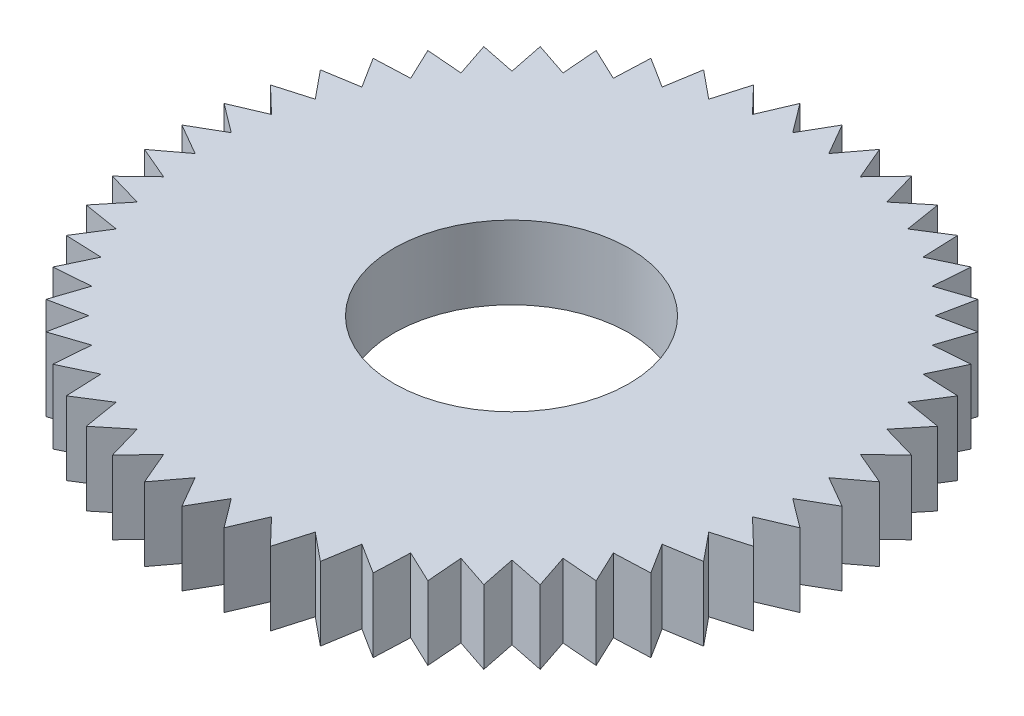
SolidWorks part; units mm, degrees
ref_plane "Front Plane" through (0, 0, 0) normal (0, 0, 1) x (1, 0, 0)
ref_plane "Top Plane" through (0, 0, 0) normal (0, 1, 0) x (1, 0, 0)
ref_plane "Right Plane" through (0, 0, 0) normal (1, 0, 0) x (0, 0, -1)
sketch "Sketch1" plane through (0, 0, 0) normal (0, 1, 0) x (1, 0, 0)
  line L0 (0, 0) -> (0, 11.2593) construction
  line L1 (0, 11.2593) -> (-0.6156, 10.1931)
  line L122 (0, 11.2593) -> (0.6156, 10.1931)
  line L123 (1.3552, 11.1774) -> (0.6156, 10.1931)
  line L124 (1.3552, 11.1774) -> (1.8377, 10.0447)
  line L125 (2.6906, 10.9326) -> (1.8377, 10.0447)
  line L126 (2.6906, 10.9326) -> (3.0331, 9.7501)
  line L127 (3.9867, 10.5287) -> (3.0331, 9.7501)
  line L128 (3.9867, 10.5287) -> (4.1842, 9.3135)
  line L129 (5.2248, 9.9715) -> (4.1842, 9.3135)
  line L130 (5.2248, 9.9715) -> (5.2744, 8.7414)
  line L131 (6.3866, 9.2692) -> (5.2744, 8.7414)
  line L132 (6.3866, 9.2692) -> (6.2876, 8.042)
  line L133 (7.4553, 8.4319) -> (6.2876, 8.042)
  line L134 (7.4553, 8.4319) -> (7.2091, 7.2256)
  line L135 (8.4153, 7.4719) -> (7.2091, 7.2256)
  line L136 (8.4153, 7.4719) -> (8.0255, 6.3041)
  line L137 (9.2526, 6.4032) -> (8.0255, 6.3041)
  line L138 (9.2526, 6.4032) -> (8.7248, 5.2909)
  line L139 (9.955, 5.2413) -> (8.7248, 5.2909)
  line L140 (9.955, 5.2413) -> (9.297, 4.2008)
  line L141 (10.5122, 4.0033) -> (9.297, 4.2008)
  line L142 (10.5122, 4.0033) -> (9.7335, 3.0497)
  line L143 (10.9161, 2.7071) -> (9.7335, 3.0497)
  line L144 (10.9161, 2.7071) -> (10.0282, 1.8543)
  line L145 (11.1608, 1.3717) -> (10.0282, 1.8543)
  line L146 (11.1608, 1.3717) -> (10.1766, 0.6321)
  line L147 (11.2428, 0.0166) -> (10.1766, 0.6321)
  line L148 (11.2428, 0.0166) -> (10.1766, -0.599)
  line L149 (11.1608, -1.3386) -> (10.1766, -0.599)
  line L150 (11.1608, -1.3386) -> (10.0282, -1.8212)
  line L151 (10.9161, -2.674) -> (10.0282, -1.8212)
  line L152 (10.9161, -2.674) -> (9.7335, -3.0165)
  line L153 (10.5122, -3.9702) -> (9.7335, -3.0165)
  line L154 (10.5122, -3.9702) -> (9.297, -4.1677)
  line L155 (9.955, -5.2082) -> (9.297, -4.1677)
  line L156 (9.955, -5.2082) -> (8.7248, -5.2578)
  line L157 (9.2526, -6.3701) -> (8.7248, -5.2578)
  line L158 (9.2526, -6.3701) -> (8.0255, -6.271)
  line L159 (8.4153, -7.4388) -> (8.0255, -6.271)
  line L160 (8.4153, -7.4388) -> (7.2091, -7.1925)
  line L161 (7.4553, -8.3988) -> (7.2091, -7.1925)
  line L162 (7.4553, -8.3988) -> (6.2876, -8.0089)
  line L163 (6.3866, -9.2361) -> (6.2876, -8.0089)
  line L164 (6.3866, -9.2361) -> (5.2744, -8.7083)
  line L165 (5.2248, -9.9384) -> (5.2744, -8.7083)
  line L166 (5.2248, -9.9384) -> (4.1842, -9.2804)
  line L167 (3.9867, -10.4956) -> (4.1842, -9.2804)
  line L168 (3.9867, -10.4956) -> (3.0331, -9.717)
  line L169 (2.6906, -10.8995) -> (3.0331, -9.717)
  line L170 (2.6906, -10.8995) -> (1.8377, -10.0116)
  line L171 (1.3552, -11.1442) -> (1.8377, -10.0116)
  line L172 (1.3552, -11.1442) -> (0.6156, -10.16)
  line L173 (0, -11.2262) -> (0.6156, -10.16)
  line L174 (0, -11.2262) -> (-0.6156, -10.16)
  line L175 (-1.3552, -11.1442) -> (-0.6156, -10.16)
  line L176 (-1.3552, -11.1442) -> (-1.8377, -10.0116)
  line L177 (-2.6906, -10.8995) -> (-1.8377, -10.0116)
  line L178 (-2.6906, -10.8995) -> (-3.0331, -9.717)
  line L179 (-3.9867, -10.4956) -> (-3.0331, -9.717)
  line L180 (-3.9867, -10.4956) -> (-4.1842, -9.2804)
  line L181 (-5.2248, -9.9384) -> (-4.1842, -9.2804)
  line L182 (-5.2248, -9.9384) -> (-5.2744, -8.7083)
  line L183 (-6.3866, -9.2361) -> (-5.2744, -8.7083)
  line L184 (-6.3866, -9.2361) -> (-6.2876, -8.0089)
  line L185 (-7.4553, -8.3988) -> (-6.2876, -8.0089)
  line L186 (-7.4553, -8.3988) -> (-7.2091, -7.1925)
  line L187 (-8.4153, -7.4388) -> (-7.2091, -7.1925)
  line L188 (-8.4153, -7.4388) -> (-8.0255, -6.271)
  line L189 (-9.2526, -6.3701) -> (-8.0255, -6.271)
  line L190 (-9.2526, -6.3701) -> (-8.7248, -5.2578)
  line L191 (-9.955, -5.2082) -> (-8.7248, -5.2578)
  line L192 (-9.955, -5.2082) -> (-9.297, -4.1677)
  line L193 (-10.5122, -3.9702) -> (-9.297, -4.1677)
  line L194 (-10.5122, -3.9702) -> (-9.7335, -3.0165)
  line L195 (-10.9161, -2.674) -> (-9.7335, -3.0165)
  line L196 (-10.9161, -2.674) -> (-10.0282, -1.8212)
  line L197 (-11.1608, -1.3386) -> (-10.0282, -1.8212)
  line L198 (-11.1608, -1.3386) -> (-10.1766, -0.599)
  line L199 (-11.2428, 0.0166) -> (-10.1766, -0.599)
  line L200 (-11.2428, 0.0166) -> (-10.1766, 0.6321)
  line L201 (-11.1608, 1.3717) -> (-10.1766, 0.6321)
  line L202 (-11.1608, 1.3717) -> (-10.0282, 1.8543)
  line L203 (-10.9161, 2.7071) -> (-10.0282, 1.8543)
  line L204 (-10.9161, 2.7071) -> (-9.7335, 3.0497)
  line L205 (-10.5122, 4.0033) -> (-9.7335, 3.0497)
  line L206 (-10.5122, 4.0033) -> (-9.297, 4.2008)
  line L207 (-9.955, 5.2413) -> (-9.297, 4.2008)
  line L208 (-9.955, 5.2413) -> (-8.7248, 5.2909)
  line L209 (-9.2526, 6.4032) -> (-8.7248, 5.2909)
  line L210 (-9.2526, 6.4032) -> (-8.0255, 6.3041)
  line L211 (-8.4153, 7.4719) -> (-8.0255, 6.3041)
  line L212 (-8.4153, 7.4719) -> (-7.2091, 7.2256)
  line L213 (-7.4553, 8.4319) -> (-7.2091, 7.2256)
  line L214 (-7.4553, 8.4319) -> (-6.2876, 8.042)
  line L215 (-6.3866, 9.2692) -> (-6.2876, 8.042)
  line L216 (-6.3866, 9.2692) -> (-5.2744, 8.7414)
  line L217 (-5.2248, 9.9715) -> (-5.2744, 8.7414)
  line L218 (-5.2248, 9.9715) -> (-4.1842, 9.3135)
  line L219 (-3.9867, 10.5287) -> (-4.1842, 9.3135)
  line L220 (-3.9867, 10.5287) -> (-3.0331, 9.7501)
  line L221 (-2.6906, 10.9326) -> (-3.0331, 9.7501)
  line L222 (-2.6906, 10.9326) -> (-1.8377, 10.0447)
  line L223 (-1.3552, 11.1774) -> (-1.8377, 10.0447)
  line L224 (-1.3552, 11.1774) -> (-0.6156, 10.1931)
  circle A0 centre (0, 0) radius 10.2117 construction
  circle A1 centre (0, 0) radius 4
  circle A2 centre (0, 0) radius 11.2593 construction
  point P4 (0, 0)
  point P164 (0, 0.0166)
  dimension "D1" = 22.5187
  dimension "D5" = 8
  dimension "D2" = 60
  dimension "D3" = 30
  dimension "D4" = 52
extrude "Boss-Extrude1" add sketch "Sketch1" along normal blind 2.5
